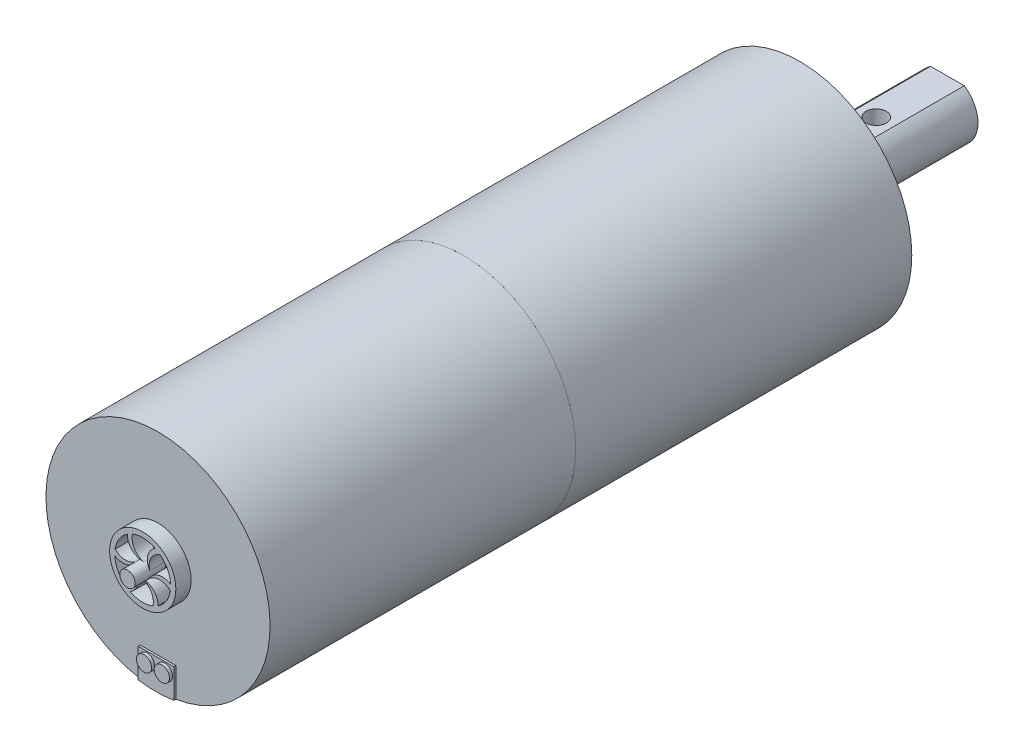
SolidWorks part; units mm, degrees
note: The reader was unsure of these and kept them because the rebuilt part matched: shared geometry of "Esquisse1<3>", "Esquisse1<4>", "Esquisse1<5>", "Esquisse1<7>", "Esquisse1<6>", "Esquisse1<8>", "Esquisse3<2>", "Esquisse6<4>", "Esquisse6<5>".
ref_plane "Plan de face" through (0, 0, 0) normal (0, 0, 1) x (1, 0, 0)
ref_plane "Plan de dessus" through (0, 0, 0) normal (0, 1, 0) x (1, 0, 0)
ref_plane "Plan de droite" through (0, 0, 0) normal (1, 0, 0) x (0, 0, -1)
sketch "Esquisse1" plane through (0, 0, 0) normal (0, 0, 1) x (1, 0, 0)
  line L0 (0, 3) -> (0, 2.5) construction
  line L1 (-6.25, 0) -> (-7.5, 0) construction
  line L2 (-1.6583, 2.5) -> (1.6583, 2.5)
  line L3 (-4.25, 0) -> (-3, 0) construction
  circle A0 centre (0, 0) radius 9.5 construction
  circle A1 centre (0, 0) radius 11
  circle A2 centre (0, 0) radius 7.5
  circle A3 centre (0, 9.5) radius 1
  circle A4 centre (8.2272, 4.75) radius 1
  circle A5 centre (8.2272, -4.75) radius 1
  circle A6 centre (0, -9.5) radius 1
  circle A7 centre (-8.2272, -4.75) radius 1
  circle A8 centre (-8.2272, 4.75) radius 1
  circle A9 centre (0, 0) radius 3
  circle A10 centre (0, 0) radius 4.25
  circle A11 centre (0, 0) radius 6.25
  point P19 (0, 0)
  dimension "D1" = 19
  dimension "D2" = 22
  dimension "D3" = 15
  dimension "D4" = 2
  dimension "D6" = 6
  dimension "D8" = 2
  dimension "D7" = 0.5
  dimension "D5" = 6
extrude "Boss.-Extru.1" add sketch "Esquisse1" along normal blind 33 contours A1 A8 A7 A6 A5 A4 A3 A2 | A2 A9 | L2 A9 | L2 A9
extrude "Boss.-Extru.2" add sketch "Esquisse1<3>" against normal blind 1.5 contours A2 A9 | L2 A9 | L2 A9
sketch "Esquisse1<3>" plane through (0, 0, 0) normal (0, 0, 1) x (1, 0, 0) same geometry as "Esquisse1"
extrude "Boss.-Extru.3" add sketch "Esquisse1<4>" against normal blind 2.5 contours L2 A9 | L2 A9
sketch "Esquisse1<4>" plane through (0, 0, 0) normal (0, 0, 1) x (1, 0, 0) same geometry as "Esquisse1"
extrude "Boss.-Extru.4" add sketch "Esquisse1<5>" against normal blind 14.5 contours L2 A9
sketch "Esquisse1<5>" plane through (0, 0, 0) normal (0, 0, 1) x (1, 0, 0) same geometry as "Esquisse1"
extrude "Boss.-Extru.5" add sketch "Esquisse1<7>" against normal blind 1.5 separate body contours A2 A11
sketch "Esquisse1<7>" plane through (0, 0, 0) normal (0, 0, 1) x (1, 0, 0) same geometry as "Esquisse1"
extrude "Boss.-Extru.6" add sketch "Esquisse1<6>" against normal blind 1 contours A11 A10
sketch "Esquisse1<6>" plane through (0, 0, 0) normal (0, 0, 1) x (1, 0, 0) same geometry as "Esquisse1"
extrude "Boss.-Extru.7" add sketch "Esquisse1<8>" along normal blind 1.5 separate body contours A10 A9
sketch "Esquisse1<8>" plane through (0, 0, 0) normal (0, 0, 1) x (1, 0, 0) same geometry as "Esquisse1"
sketch "Esquisse2" plane through (0, 2.5, 0) normal (0, 1, 0) x (1, 0, 0)
  line L0 (0, 7.5) -> (0, 2.5) construction
  line L1 (-1.6583, 2.5) -> (1.6583, 2.5) construction
  circle A0 centre (0, 7.5) radius 1
  dimension "D1" = 5
  dimension "D2" = 2
extrude "Enlèv. mat.-Extru.1" cut sketch "Esquisse2" against normal up to next
sketch "Esquisse3" plane through (0, 0, 33) normal (0, 0, 1) x (1, 0, 0)
  circle A0 centre (0, 0) radius 11
  circle A1 centre (0, 0) radius 11 construction
extrude "Boss.-Extru.8" add sketch "Esquisse3" along normal blind 30 separate body
extrude "Boss.-Extru.9" add sketch "Esquisse3<2>" against normal blind 27
sketch "Esquisse3<2>" plane through (0, 0, 33) normal (0, 0, 1) x (1, 0, 0) same geometry as "Esquisse3"
sketch "Esquisse4" plane through (0, 0, 63) normal (0, 0, 1) x (1, 0, 0)
  circle A0 centre (0, 0) radius 0.75 construction
  circle A1 centre (0, 0) radius 2.75
  arc A2 (0, 0.75) -> (-1.499, 2.3056) centre (0, 2.25) cw
  arc A3 (0.1, 0.7433) -> (-0.999, 2.5621) centre (0.4567, 2.2003) cw
  arc A4 (0.6495, 0.375) -> (1.2472, 2.4509) centre (1.9486, 1.125) cw
  arc A5 (0.6937, 0.285) -> (1.7194, 2.1462) centre (2.1339, 0.7046) cw
  arc A6 (0.6495, -0.375) -> (2.7462, 0.1454) centre (1.9486, -1.125) cw
  arc A7 (0.5937, -0.4583) -> (2.7184, -0.4159) centre (1.6771, -1.4957) cw
  arc A8 (0, -0.75) -> (1.499, -2.3056) centre (0, -2.25) cw
  arc A9 (-0.1, -0.7433) -> (0.999, -2.5621) centre (-0.4567, -2.2003) cw
  arc A10 (-0.6495, -0.375) -> (-1.2472, -2.4509) centre (-1.9486, -1.125) cw
  arc A11 (-0.6937, -0.285) -> (-1.7194, -2.1462) centre (-2.1339, -0.7046) cw
  arc A12 (-0.6495, 0.375) -> (-2.7462, -0.1454) centre (-1.9486, 1.125) cw
  arc A13 (-0.5937, 0.4583) -> (-2.7184, 0.4159) centre (-1.6771, 1.4957) cw
  arc A14 (-0.5937, 0.4583) -> (0, 0.75) centre (0, 0) cw
  arc A15 (0.1, 0.7433) -> (0.6495, 0.375) centre (0, 0) cw
  arc A16 (0.6937, 0.285) -> (0.6495, -0.375) centre (0, 0) cw
  arc A17 (0.5937, -0.4583) -> (0, -0.75) centre (0, 0) cw
  arc A18 (-0.1, -0.7433) -> (-0.6495, -0.375) centre (0, 0) cw
  arc A19 (-0.6937, -0.285) -> (-0.6495, 0.375) centre (0, 0) cw
  circle A21 centre (0, 0) radius 3.25
  point P42 (0, 0)
  dimension "D1" = 1.5
  dimension "D2" = 5.5
  dimension "D3" = 1.5
  dimension "D4" = 0.5
  dimension "D7" = 0.5
  dimension "D5" = 0.1
  dimension "D6" = 6
extrude "Boss.-Extru.10" add sketch "Esquisse4" along normal blind 1.5 contours A19 A11 A1 A10 A18 A9 A8 A17 A7 A6 A16 A5 A4 A15 A3 A2 A14 A13 A12 | A21 A1
sketch "Esquisse5" plane through (0, 0, 64.5) normal (0, 0, 1) x (1, 0, 0)
  circle A0 centre (0, 0) radius 0.75
  arc A1 (0, 0.75) -> (-0.5937, 0.4583) centre (0, 0) ccw construction
extrude "Boss.-Extru.11" add sketch "Esquisse5" along normal blind 1.5
chamfer "Chanfrein1" distance 0.5 angle 45 1 edges at (6.25, 0, -1.5)
sketch "Esquisse6" plane through (0, 0, 63) normal (0, 0, 1) x (1, 0, 0)
  line L0 (0, -9.5) -> (0, -8) construction
  line L1 (1.75, -8) -> (-1.75, -8)
  line L2 (1.75, -8) -> (1.75, -11) construction
  line L3 (1.75, -11) -> (-1.75, -11) construction
  line L4 (-1.75, -8) -> (-1.75, -11) construction
  line L5 (1.75, -8) -> (-1.75, -11) construction
  line L6 (1.75, -11) -> (-1.75, -8) construction
  line L7 (-1.75, -8) -> (-1.75, -10.8599)
  line L8 (1.75, -10.8599) -> (1.75, -8)
  circle A0 centre (0, 0) radius 11 construction
  circle A1 centre (-0.875, -8.875) radius 0.75
  circle A2 centre (0.875, -8.875) radius 0.75
  arc A3 (-1.75, -10.8599) -> (1.75, -10.8599) centre (0, 0) ccw
  point P0 (0, -9.5)
  dimension "D2" = 1.5
  dimension "D1" = 3
  dimension "D3" = 3.5
  dimension "D4" = 0.875
  dimension "D5" = 0.875
extrude "Boss.-Extru.15" add sketch "Esquisse6" along normal blind 0.2
extrude "Boss.-Extru.16" add sketch "Esquisse6<4>" along normal blind 0.5 contours A1
sketch "Esquisse6<4>" plane through (0, 0, 63) normal (0, 0, 1) x (1, 0, 0) same geometry as "Esquisse6"
extrude "Boss.-Extru.17" add sketch "Esquisse6<5>" along normal blind 0.5 contours A2
sketch "Esquisse6<5>" plane through (0, 0, 63) normal (0, 0, 1) x (1, 0, 0) same geometry as "Esquisse6"
